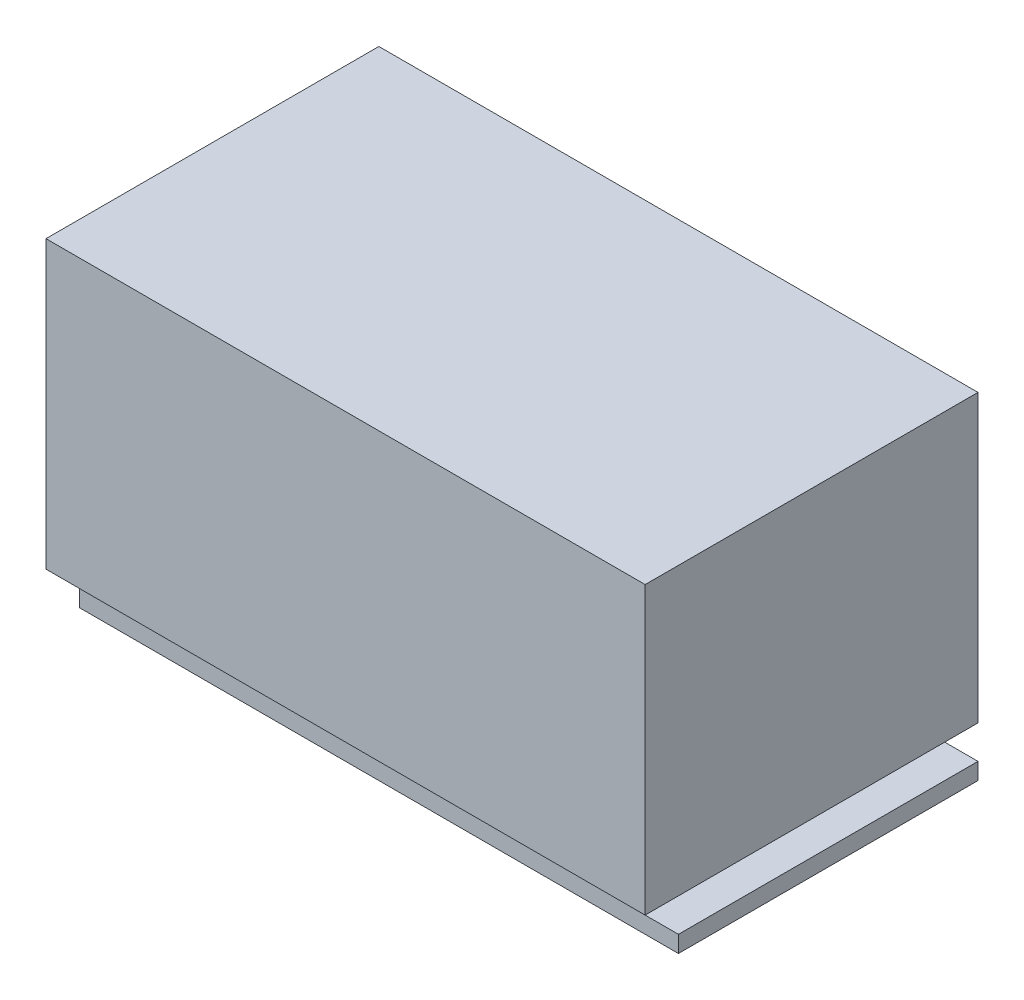
SolidWorks part; units mm, degrees
ref_plane "Front Plane" through (0, 0, 0) normal (0, 0, 1) x (1, 0, 0)
ref_plane "Top Plane" through (0, 0, 0) normal (0, 1, 0) x (1, 0, 0)
ref_plane "Right Plane" through (0, 0, 0) normal (1, 0, 0) x (0, 0, -1)
sketch "Sketch1" plane through (0, 0, 0) normal (0, 1, 0) x (1, 0, 0)
  line L1 (0, 0) -> (54, 0)
  line L2 (0, 0) -> (0, 27)
  line L3 (0, 27) -> (54, 27)
  line L4 (54, 0) -> (54, 27)
  dimension "D1" = 54
  dimension "D2" = 27
extrude "Boss-Extrude1" add sketch "Sketch1" along normal blind 1.5
sketch "Sketch2" plane through (0, 1.5, 0) normal (0, 1, 0) x (1, 0, 0)
  line L0 (0, 27) -> (0, 0) construction
  circle A0 centre (5.8, 13.5) radius 2.25
  point P5 (0, 13.5)
  dimension "D3" = 4.5
  dimension "D1" = 5.8
extrude "Cut-Extrude1" cut sketch "Sketch2" against normal up to next and the other way through all
ref_plane "Plane1" through (27, 0, 0) normal (-1, 0, 0) x (0, 0, 1)
mirror "Mirror1" about plane through (27, 0, 0) normal (-1, 0, 0) of "Cut-Extrude1"
sketch "Sketch3" plane through (0, 1.5, 0) normal (0, 1, 0) x (1, 0, 0)
  line L0 (54, 27) -> (0, 27) construction
  line L1 (13.8, 27) -> (40.2, 27)
  line L2 (13.8, 27) -> (13.8, -3)
  line L3 (13.8, -3) -> (40.2, -3)
  line L4 (40.2, 27) -> (40.2, -3)
  line L7 (0, 0) -> (54, 0) construction
  circle A0 centre (5.8, 13.5) radius 2.25 construction
  point P8 (27, 0)
  point P9 (27, -3)
  dimension "D1" = 8
  dimension "D2" = 3
extrude "Boss-Extrude2" add sketch "Sketch3" along normal blind 3
chamfer "Chamfer3" distance 3 angle 45 1 edges at (27, 1.5, 3)
sketch "Sketch27" plane through (0, 4.5, 0) normal (0, 1, 0) x (1, 0, 0)
  line L0 (40.2, 27) -> (13.8, 27) construction
  line L1 (0, 27) -> (54, 27)
  line L2 (0, 27) -> (0, -3)
  line L3 (0, -3) -> (54, -3)
  line L4 (54, 27) -> (54, -3)
  line L5 (54, 0) -> (54, 27) construction
  line L6 (0, 27) -> (0, 0) construction
  line L7 (13.8, -3) -> (40.2, -3) construction
extrude "Boss-Extrude20" add sketch "Sketch27" along normal offset from surface (25.8 mm away) 30.3 up to face at (48.2, 0, -15.75)
